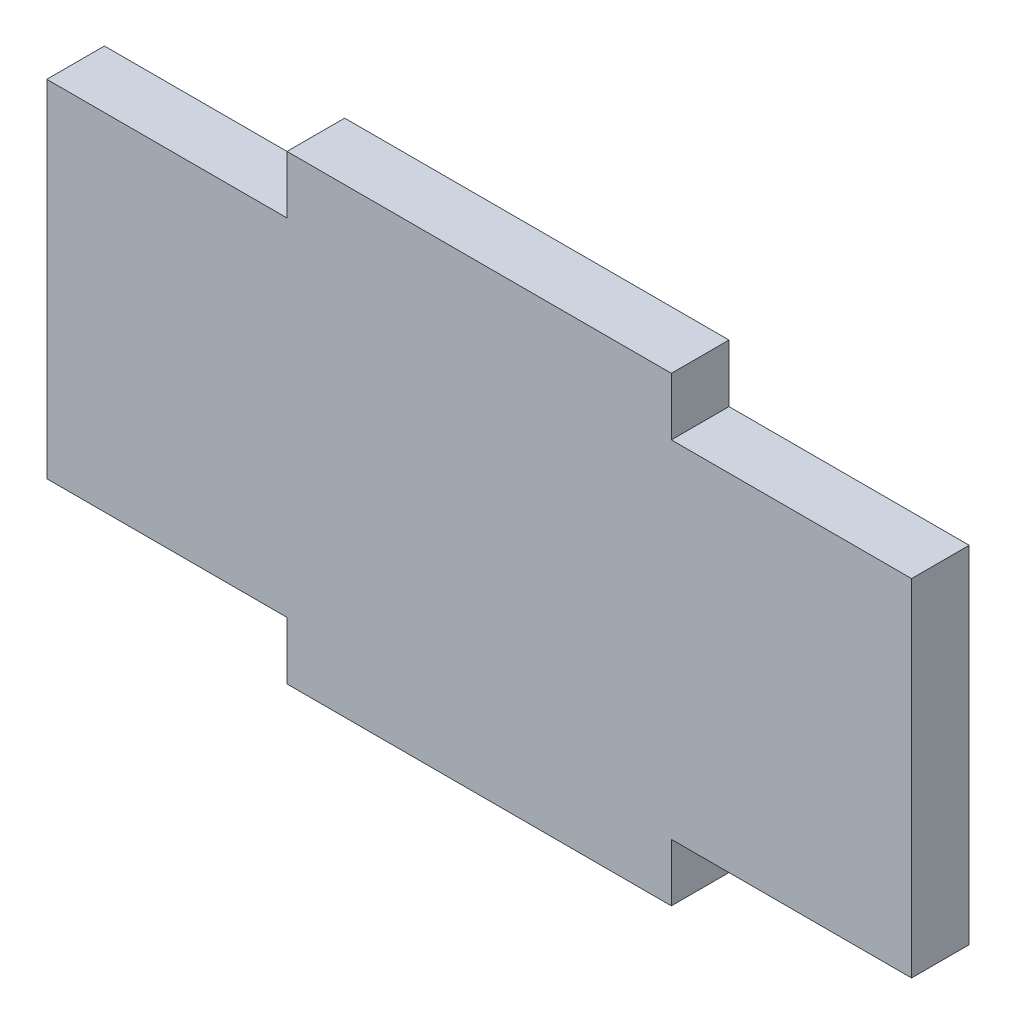
SolidWorks part; units mm, degrees
ref_plane "Plano frontal" through (0, 0, 0) normal (0, 0, 1) x (1, 0, 0)
ref_plane "Plano superior" through (0, 0, 0) normal (0, 1, 0) x (1, 0, 0)
ref_plane "Plano direito" through (0, 0, 0) normal (1, 0, 0) x (0, 0, -1)
sketch "Esboço1" plane through (0, 0, 0) normal (0, 0, 1) x (1, 0, 0)
  line L0 (0, 0) -> (22.5, 0) construction
  line L1 (-22.5, -9) -> (22.5, -9)
  line L2 (-22.5, -9) -> (-22.5, 9)
  line L3 (-22.5, 9) -> (22.5, 9)
  line L4 (22.5, -9) -> (22.5, 9)
  line L5 (-22.5, -9) -> (22.5, 9) construction
  line L6 (-22.5, 9) -> (22.5, -9) construction
  line L7 (10, 12) -> (-10, 12)
  line L8 (10, 12) -> (10, 9)
  line L9 (10, 9) -> (-10, 9)
  line L10 (-10, 12) -> (-10, 9)
  line L11 (10, 12) -> (-10, 9) construction
  line L12 (10, 9) -> (-10, 12) construction
  line L13 (10, -9) -> (-10, -9)
  line L14 (-10, -12) -> (-10, -9)
  line L15 (10, -12) -> (-10, -12)
  line L16 (10, -12) -> (10, -9)
  point P0 (0, 0)
  point P6 (0, 10.5)
  dimension "D1" = 3
  dimension "D2" = 20
  dimension "D3" = 45
  dimension "D4" = 18
extrude "Ressalto-extrusão1" add sketch "Esboço1" along normal blind 3 contours L1 L4 L3 L2 | L7 L10 L3 L8 | L15 L16 L1 L14 region at (0, 0, 0) region at (0, -10.5, 0) region at (0, 10.5, 0)
